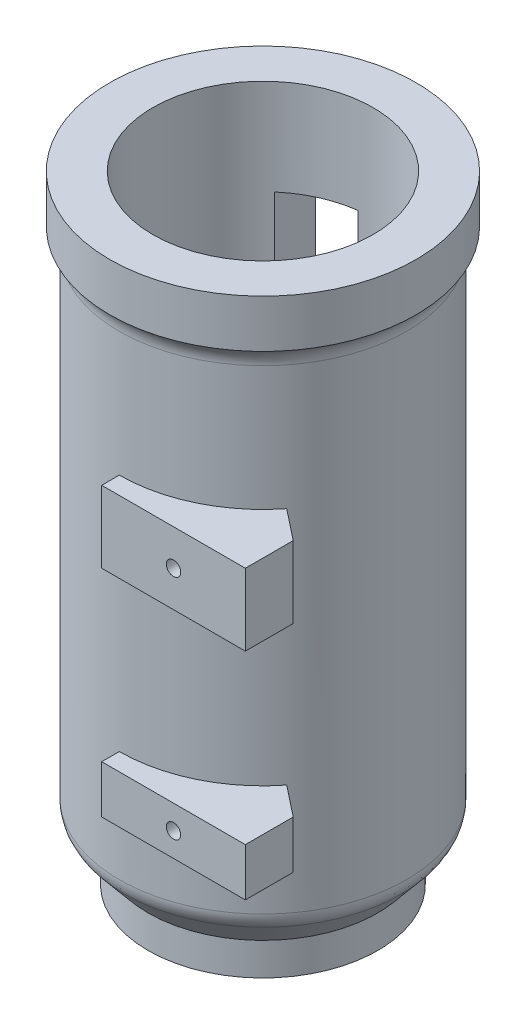
SolidWorks part; units mm, degrees
ref_plane "Alzado" through (0, 0, 0) normal (0, 0, 1) x (1, 0, 0)
ref_plane "Planta" through (0, 0, 0) normal (0, 1, 0) x (1, 0, 0)
ref_plane "Vista lateral" through (0, 0, 0) normal (1, 0, 0) x (0, 0, -1)
sketch "Croquis1" plane through (0, 0, 0) normal (0, 1, 0) x (1, 0, 0)
  circle A0 centre (0, 0) radius 22.5
  dimension "D1" = 45
ref_plane "Plano1" through (0, 9, 0) normal (0, 1, 0) x (1, 0, 0)
sketch "Croquis2" plane through (0, 9, 0) normal (0, 1, 0) x (1, 0, 0)
  circle A0 centre (0, 0) radius 30
  dimension "D1" = 60
loft "Recubrir1" add profiles "Croquis1", "Croquis2" connector at (-22.5, 0, 0) connector at (-29.9996, 9, 0.1611)
sketch "Croquis3" plane through (0, 9, 0) normal (0, 1, 0) x (1, 0, 0)
  circle A1 centre (0, 0) radius 30 construction
  circle A2 centre (0, 0) radius 30
extrude "Saliente-Extruir1" add sketch "Croquis3" along normal blind 105
sketch "Croquis4" plane through (0, 114, 0) normal (0, 1, 0) x (1, 0, 0)
  circle A0 centre (0, 0) radius 32
  dimension "D1" = 64
extrude "Saliente-Extruir2" add sketch "Croquis4" along normal blind 10
sketch "Croquis6" plane through (0, 124, 0) normal (0, 1, 0) x (1, 0, 0)
  circle A0 centre (0, 0) radius 23
  dimension "D1" = 46
extrude "Cortar-Extruir1" cut sketch "Croquis6" against normal blind 161
sketch "Croquis7" plane through (0, 0, 0) normal (0, 1, 0) x (1, 0, 0)
  circle A0 centre (0, 0) radius 23
  circle A1 centre (0, 0) radius 24
  dimension "D1" = 48
  dimension "D2" = 46
extrude "Saliente-Extruir3" add sketch "Croquis7" against normal blind 5 and the other way blind 3
fillet "Redondeo1" radius 5 2 edges at (0, 9, 30) (0, 114, 30)
sketch "Croquis9" plane through (0, 0, 0) normal (0, 0, 1) x (1, 0, 0)
  line L0 (0, 124) -> (0, 0) construction
  line L1 (32, 124) -> (-32, 124) construction
  line L3 (-15, 104) -> (-3, 104)
  line L4 (-15, 104) -> (-15, 64)
  line L5 (-15, 64) -> (-3, 64)
  line L6 (-3, 104) -> (-3, 64)
  dimension "D1" = 12
  dimension "D2" = 40
  dimension "D3" = 64
  dimension "D4" = 15
extrude "Cortar-Extruir2" cut sketch "Croquis9" against normal blind 525
ref_plane "Plano2" through (0, 84, 0) normal (0, 1, 0) x (1, 0, 0)
sketch "Croquis10" plane through (0, 84, 0) normal (0, 1, 0) x (1, 0, 0)
  line L0 (0, -30) -> (0, -33.6756)
  line L1 (0, -33.6756) -> (30, -33.6756)
  line L2 (30, -33.6756) -> (30, -23.6756)
  line L3 (0, 0) -> (0, -72.522) construction
  line L4 (30, -23.6756) -> (23.5498, -18.5852)
  circle A0 centre (0, 0) radius 30 construction
  arc A1 (0, -30) -> (23.5498, -18.5852) centre (0, 0) ccw
  dimension "D3" = 51.72
  dimension "D1" = 30
  dimension "D2" = 10
extrude "Saliente-Extruir4" add sketch "Croquis10" against normal blind 15
ref_plane "Plano3" through (0, 24, 0) normal (0, 1, 0) x (1, 0, 0)
sketch "Croquis11" plane through (0, 24, 0) normal (0, 1, 0) x (1, 0, 0)
  line L4 (30, -23.6756) -> (23.5498, -18.5852)
  line L5 (0, -30) -> (0, -33.6756)
  line L6 (0, -33.6756) -> (30, -33.6756)
  line L7 (30, -33.6756) -> (30, -23.6756)
  line L8 (30, -23.6756) -> (23.5498, -18.5852)
  line L9 (0, -30) -> (0, -33.6756)
  line L10 (0, -33.6756) -> (30, -33.6756)
  line L11 (30, -33.6756) -> (30, -23.6756)
  arc A1 (0, -30) -> (23.5498, -18.5852) centre (0, 0) ccw
  arc A2 (0, -30) -> (23.5498, -18.5852) centre (0, 0) ccw
  dimension "D1" = 0
extrude "Saliente-Extruir5" add sketch "Croquis11" along normal blind 10
sketch "Croquis12" plane through (0, 0, 33.6756) normal (0, 0, 1) x (1, 0, 0)
  line L0 (0, 69) -> (30, 84) construction
  line L1 (0, 24) -> (30, 34) construction
  circle A0 centre (15, 29) radius 1.5
  circle A1 centre (15, 76.5) radius 1.5
  dimension "D1" = 3
  dimension "D2" = 3
extrude "Cortar-Extruir3" cut sketch "Croquis12" against normal blind 13
